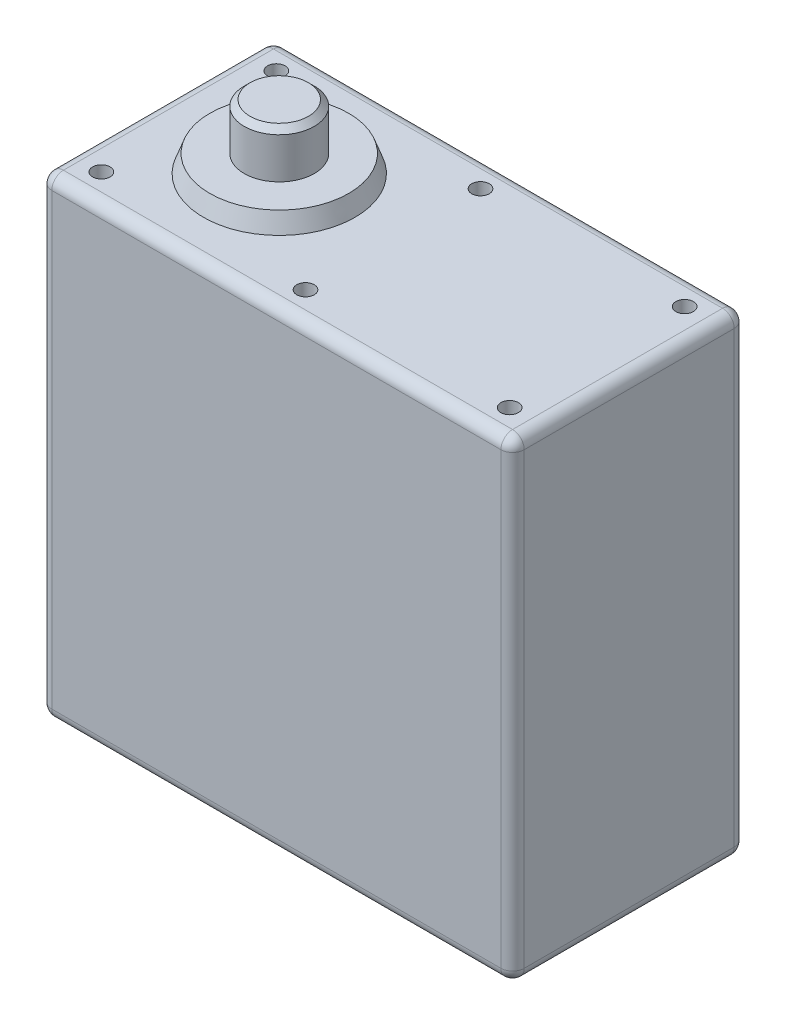
SolidWorks part; units mm, degrees
ref_plane "前基準面" through (0, 0, 0) normal (0, 0, 1) x (1, 0, 0)
ref_plane "上基準面" through (0, 0, 0) normal (0, 1, 0) x (1, 0, 0)
ref_plane "右基準面" through (0, 0, 0) normal (1, 0, 0) x (0, 0, -1)
sketch "草圖1" plane through (0, 0, 0) normal (0, 0, 1) x (1, 0, 0)
  line L1 (-20.25, 20.25) -> (20.25, 20.25)
  line L2 (-20.25, 20.25) -> (-20.25, -20.25)
  line L3 (-20.25, -20.25) -> (20.25, -20.25)
  line L4 (20.25, 20.25) -> (20.25, -20.25)
  dimension "D1" = 20.25
  dimension "D2" = 40.5
  dimension "D3" = 40.5
  dimension "D4" = 20.25
extrude "伸長1" add sketch "草圖1" along normal blind 20
sketch "草圖2" plane through (0, 20.25, 0) normal (0, 1, 0) x (1, 0, 0)
  line L0 (-20.25, -20) -> (-20.25, 0) construction
  line L2 (20.25, -20) -> (-20.25, -20) construction
  circle A0 centre (-9.75, -10) radius 6.5
  dimension "D1" = 13
  dimension "D2" = 10.5
  dimension "D3" = 10
extrude "伸長2" add sketch "草圖2" along normal blind 1.5
sketch "草圖5" plane through (0, 20.25, 0) normal (0, 1, 0) x (1, 0, 0)
  line L0 (20.25, -10) -> (-20.25, -10) construction
  line L1 (20.25, -20) -> (20.25, 0) construction
  line L2 (-20.25, -20) -> (-20.25, 0) construction
  line L3 (-9.75, -3.5) -> (-9.75, -16.9582) construction
  circle A0 centre (-17.5, -2.5) radius 0.75
  circle A1 centre (0, -2.5) radius 0.75
  circle A2 centre (17.5, -2.5) radius 0.75
  circle A3 centre (17.5, -17.5) radius 0.75
  circle A4 centre (0, -17.5) radius 0.75
  circle A5 centre (-17.5, -17.5) radius 0.75
  circle A6 centre (-9.75, -10) radius 6.5 construction
  circle A7 centre (-9.75, -10) radius 6.5 construction
  dimension "D4" = 1.5
  dimension "D5" = 1.5
  dimension "D6" = 1.5
  dimension "D1" = 7.5
  dimension "D2" = 7.5
  dimension "D3" = 7.5
  dimension "D7" = 9.75
  dimension "D8" = 17.5
  dimension "D9" = 17.5
extrude "除料-伸長1" cut sketch "草圖5" against normal through all
sketch "草圖12" plane through (0, 21.75, 0) normal (0, 1, 0) x (1, 0, 0)
  circle A0 centre (-9.75, -10) radius 3
  dimension "D1" = 6
extrude "伸長3" add sketch "草圖12" along normal blind 4
chamfer "導角1" distance 1.5 angle 20 1 edges at (-9.75, 21.75, 16.5) first distance on face at (-9.75, 21.75, 16.5)
chamfer "導角2" distance 0.5 angle 45 1 edges at (-9.75, 25.75, 13)
sketch "草圖18" plane through (0, -20.25, 0) normal (0, -1, 0) x (1, 0, 0)
  circle A0 centre (-9.75, 10) radius 1.25
  circle A1 centre (-9.75, 10) radius 3
  dimension "D1" = 2.5
  dimension "D2" = 6
extrude "伸長4" add sketch "草圖18" along normal blind 1.5
fillet "圓角2" radius 1 4 edges at (20.25, 0, 20) (20.25, 0, 0) (-20.25, 0, 0) (-20.25, 0, 20)
fillet "圓角3" radius 1 16 edges at (19.9571, -20.25, 19.7071) (0, -20.25, 20) (-19.9571, -20.25, 19.7071) (-20.25, -20.25, 10) (-19.9571, -20.25, 0.2929) (0, -20.25, 0) (19.9571, -20.25, 0.2929) (20.25, -20.25, 10) (19.9571, 20.25, 19.7071) (0, 20.25, 20) (-19.9571, 20.25, 19.7071) (-20.25, 20.25, 10) (-19.9571, 20.25, 0.2929) (19.9571, 20.25, 0.2929) (0, 20.25, 0) (20.25, 20.25, 10)
